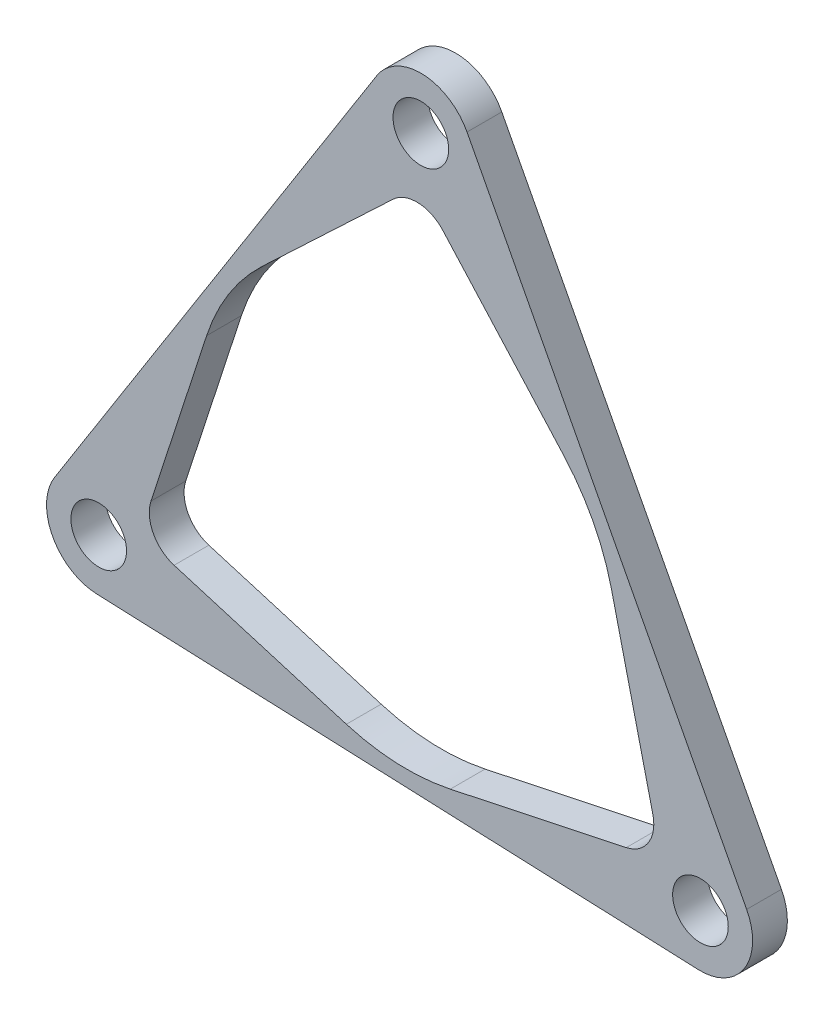
SolidWorks part; units mm, degrees
material "Thornel Mat VMA"
ref_plane "Front Plane" through (0, 0, 0) normal (0, 0, 1) x (1, 0, 0)
ref_plane "Top Plane" through (0, 0, 0) normal (0, 1, 0) x (1, 0, 0)
ref_plane "Right Plane" through (0, 0, 0) normal (1, 0, 0) x (0, 0, -1)
sketch "Sketch1" plane through (0, 0, 0) normal (0, 0, 1) x (1, 0, 0)
  line L0 (-1.7199, 21.588) -> (-20.2484, -7.6813)
  line L1 (3.4719, 21.3763) -> (19.5557, -9.3045)
  line L2 (-17.8358, -12.2835) -> (16.7764, -13.6949)
  line L3 (-0.7838, 15.8999) -> (-8.3062, 8.7987)
  line L4 (0.7057, 17.3061) -> (-15.3404, -8.0419) construction
  line L5 (-15.3404, -8.0419) -> (14.6347, -9.2642) construction
  line L6 (14.6347, -9.2642) -> (0.7057, 17.3061) construction
  line L7 (2.0759, 15.7833) -> (8.995, 8.0932)
  line L8 (-3.4668, -11.5927) -> (-13.3778, -8.6288)
  line L9 (-14.7067, -6.0939) -> (-11.5064, 3.7433)
  line L10 (11.773, 2.794) -> (14.1617, -7.2711)
  line L11 (12.6308, -9.6894) -> (2.5114, -11.8365)
  circle A0 centre (0.8149, 19.9834) radius 3
  circle A1 centre (-17.7136, -9.286) radius 3
  circle A2 centre (16.8987, -10.6974) radius 3
  circle A3 centre (0, 0) radius 12.1
  circle A4 centre (0, 0) radius 8.6603 construction
  arc A5 (2.4635, 19.9162) -> (-0.8337, 20.0506) centre (0.8149, 19.9834) ccw construction
  arc A6 (14.1617, -7.2711) -> (12.6308, -9.6894) centre (12.2157, -7.733) cw
  arc A7 (-13.3778, -8.6288) -> (-14.7067, -6.0939) centre (-12.8048, -6.7126) cw
  arc A8 (-0.7838, 15.8999) -> (2.0759, 15.7833) centre (0.5891, 14.4456) cw
  circle A9 centre (0.8149, 19.9834) radius 1.6
  circle A10 centre (-17.7136, -9.286) radius 1.6
  circle A11 centre (16.8987, -10.6974) radius 1.6
  point P35 (0, 0)
  dimension "D1" = 6
  dimension "D4" = 24.2
  dimension "D2" = 2
  dimension "D5" = 3.2
  dimension "D3" = 30
extrude "Boss-Extrude1" add sketch "Sketch1" along normal blind 2 contours A2 L1 A0 L0 A1 L2 L3 A8 L7 A3 L10 A6 L11 L8 A7 L9 | A0 A9 | A2 A11 | A1 A10 region at (-0.1685, 16.5912, 0) region at (0.9337, 22.8961, 0) region at (-16.9019, -6.4861, 0) region at (19.7293, -10.0005, 0)
